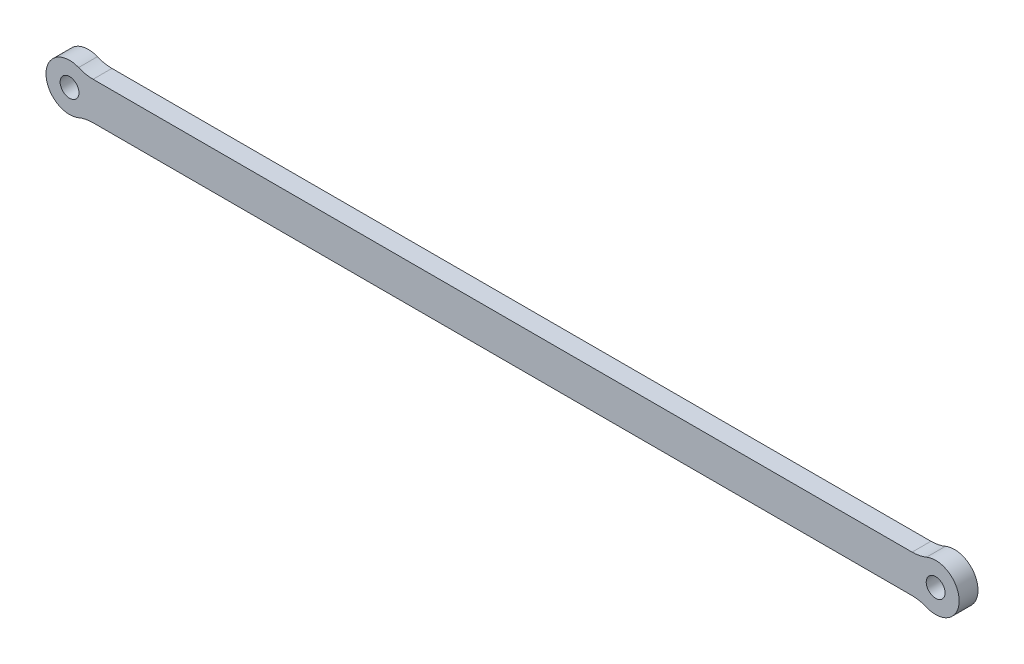
SolidWorks part; units mm, degrees
ref_plane "Ebene vorne" through (0, 0, 0) normal (0, 0, 1) x (1, 0, 0)
ref_plane "Ebene oben" through (0, 0, 0) normal (0, 1, 0) x (1, 0, 0)
ref_plane "Ebene rechts" through (0, 0, 0) normal (1, 0, 0) x (0, 0, -1)
sketch "Skizze1" plane through (0, 0, 0) normal (0, 0, 1) x (1, 0, 0)
  line L0 (-115, 0) -> (115, 0) construction
  line L1 (-108.75, 5) -> (108.75, 5)
  line L2 (-108.75, -5) -> (108.75, -5)
  line L4 (0, 5) -> (0, -5) construction
  circle A2 centre (-115, 0) radius 2.5
  arc A4 (-112.5962, 5.7692) -> (-112.5962, -5.7692) centre (-115, 0) ccw
  arc A5 (-108.75, -5) -> (-112.5962, -5.7692) centre (-108.75, -15) ccw
  arc A6 (-108.75, 5) -> (-112.5962, 5.7692) centre (-108.75, 15) cw
  arc A7 (108.75, 5) -> (112.5962, 5.7692) centre (108.75, 15) ccw
  arc A8 (108.75, -5) -> (112.5962, -5.7692) centre (108.75, -15) cw
  arc A9 (112.5962, 5.7692) -> (112.5962, -5.7692) centre (115, 0) cw
  circle A10 centre (115, 0) radius 2.5
  point P2 (0, 0)
  point P15 (0, 0)
  dimension "D3" = 5
  dimension "D4" = 12.5
  dimension "D5" = 10
  dimension "D1" = 10
  dimension "D2" = 115
extrude "Aufsatz-Linear austragen1" add sketch "Skizze1" along normal blind 5 contours L2 L1 A2 region at (0, 0, 0)
